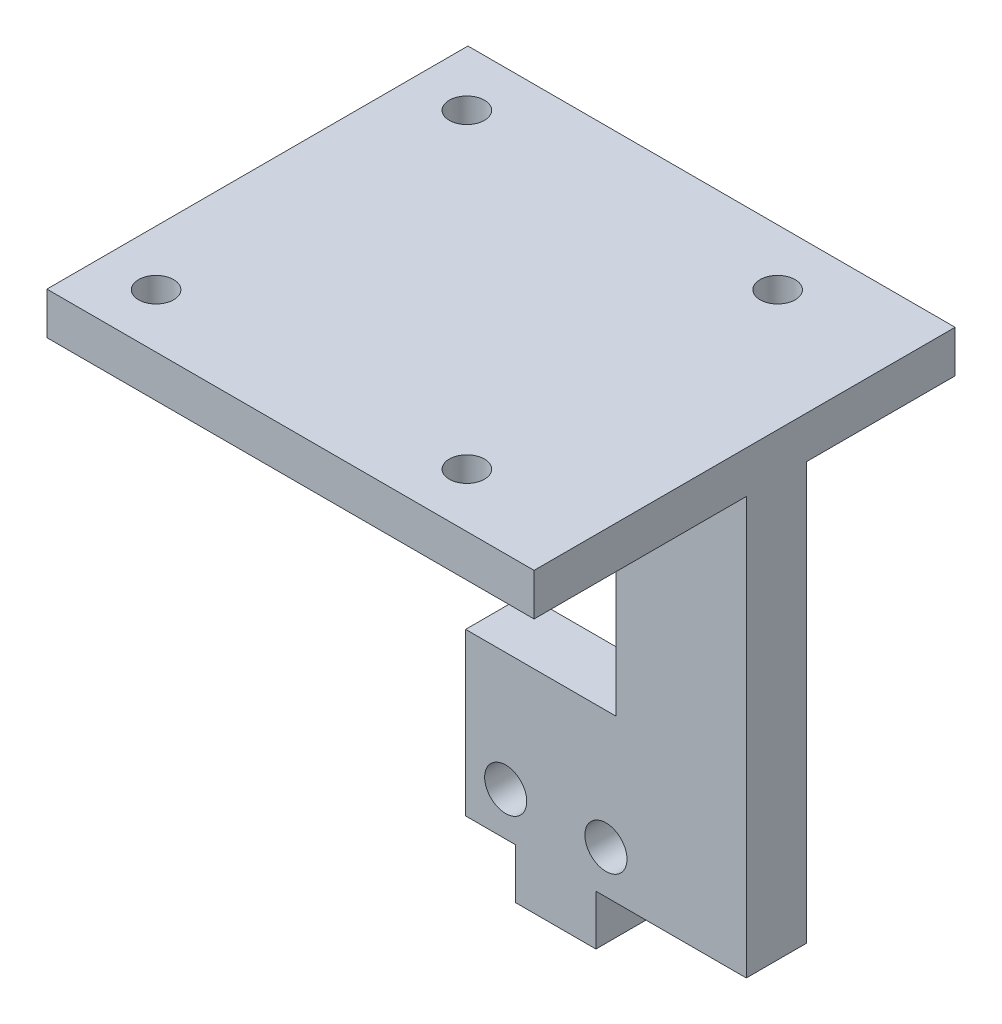
SolidWorks part; units mm, degrees
ref_plane "前视基准面" through (0, 0, 0) normal (0, 0, 1) x (1, 0, 0)
ref_plane "上视基准面" through (0, 0, 0) normal (0, 1, 0) x (1, 0, 0)
ref_plane "右视基准面" through (0, 0, 0) normal (1, 0, 0) x (0, 0, -1)
sketch "草图1" plane through (0, 0, 0) normal (0, 0, 1) x (1, 0, 0)
  line L1 (0, 0) -> (18, 0)
  line L2 (0, 0) -> (0, 50)
  line L3 (0, 50) -> (18, 50)
  line L4 (18, 0) -> (18, 50)
  dimension "D1" = 18
  dimension "D2" = 50
extrude "凸台-拉伸1" add sketch "草图1" along normal blind 6
sketch "草图3" plane through (0, 0, 6) normal (0, 0, 1) x (1, 0, 0)
  line L0 (9, 0) -> (9, 21.4804) construction
  line L1 (0, 0) -> (18, 0) construction
  circle A0 centre (4, 4.3045) radius 2.1
  circle A1 centre (14, 4.3045) radius 2.1
  dimension "D1" = 4.2
  dimension "D2" = 10
  dimension "D3" = 4.3045
extrude "切除-拉伸2" cut sketch "草图3" against normal blind 6
sketch "草图4" plane through (0, 0, 0) normal (0, -1, 0) x (1, 0, 0)
  line L0 (9, 6) -> (9, -13.3054) construction
  line L1 (0, 6) -> (18, 6) construction
  line L3 (13, 6) -> (5, 6)
  line L4 (13, 6) -> (13, -4)
  line L5 (13, -4) -> (5, -4)
  line L6 (5, 6) -> (5, -4)
  dimension "D1" = 8
  dimension "D2" = 10
extrude "凸台-拉伸2" add sketch "草图4" along normal blind 5
sketch "草图5" plane through (18, 0, 0) normal (1, 0, 0) x (0, 0, -1)
  line L0 (-6, 0) -> (-6, 50) construction
  line L1 (0, 0) -> (-6, 0)
  line L2 (0, 0) -> (0, 50)
  line L3 (0, 50) -> (-6, 50)
  line L4 (-6, 0) -> (-6, 50)
  line L5 (-6, 50) -> (0, 50) construction
  dimension "D1" = 0
extrude "凸台-拉伸3" add sketch "草图5" along normal blind 10
sketch "草图6" plane through (0, 0, 6) normal (0, 0, 1) x (1, 0, 0)
  line L0 (0, 50) -> (0, 0) construction
  line L1 (0, 16.1194) -> (15, 16.1194)
  line L2 (0, 16.1194) -> (0, 50)
  line L3 (0, 50) -> (15, 50)
  line L4 (15, 16.1194) -> (15, 50)
  line L5 (28, 50) -> (0, 50) construction
  dimension "D1" = 15
extrude "切除-拉伸3" cut sketch "草图6" against normal blind 10
sketch "草图7" plane through (0, 50, 0) normal (0, 1, 0) x (1, 0, 0)
  line L1 (28, -6) -> (9.8054, -6)
  line L2 (28, -6) -> (28, 2.4383)
  line L3 (28, 2.4383) -> (9.8054, 2.4383)
  line L4 (9.8054, -6) -> (9.8054, 2.4383)
extrude "切除-拉伸4" cut sketch "草图7" against normal blind 4.2
sketch "草图8" plane through (0, 45.8, 0) normal (0, 1, 0) x (1, 0, 0)
  line L0 (15, -6) -> (28, -6) construction
  line L1 (28, -27.17) -> (-30.5473, -27.17)
  line L2 (28, -27.17) -> (28, 14.83)
  line L3 (28, 14.83) -> (-30.5473, 14.83)
  line L4 (-30.5473, -27.17) -> (-30.5473, 14.83)
  line L5 (15, 0) -> (28, 0) construction
  dimension "D1" = 21.17
  dimension "D2" = 14.83
extrude "凸台-拉伸4" add sketch "草图8" against normal blind 4.2
sketch "草图9" plane through (-30.5473, 0, 0) normal (-1, 0, 0) x (0, 0, 1)
  line L1 (27.17, 45.8) -> (-22.0558, 45.8)
  line L2 (27.17, 45.8) -> (27.17, 39.7485)
  line L3 (27.17, 39.7485) -> (-22.0558, 39.7485)
  line L4 (-22.0558, 45.8) -> (-22.0558, 39.7485)
extrude "切除-拉伸5" cut sketch "草图9" against normal blind 9.95
sketch "草图15" plane through (0, 41.6, 0) normal (0, -1, 0) x (1, 0, 0)
  line L0 (0.4024, -12.4657) -> (0.4024, 23.6426) construction
  line L1 (0.4024, 6.2762) -> (-16.0251, 6.2762) construction
  line L2 (28, -14.83) -> (-20.5973, -14.83) construction
  line L3 (28, 0) -> (28, -14.83) construction
  circle A0 centre (15.9024, -9.2238) radius 1.75
  circle A1 centre (-15.0976, -9.2238) radius 1.75
  circle A2 centre (15.9024, 21.7762) radius 1.75
  circle A3 centre (-15.0976, 21.7762) radius 1.75
  dimension "D1" = 3.5
  dimension "D2" = 31
  dimension "D3" = 31
  dimension "D4" = 5.6062
  dimension "D5" = 12.0976
extrude "切除-拉伸6" cut sketch "草图15" against normal blind 9.95
